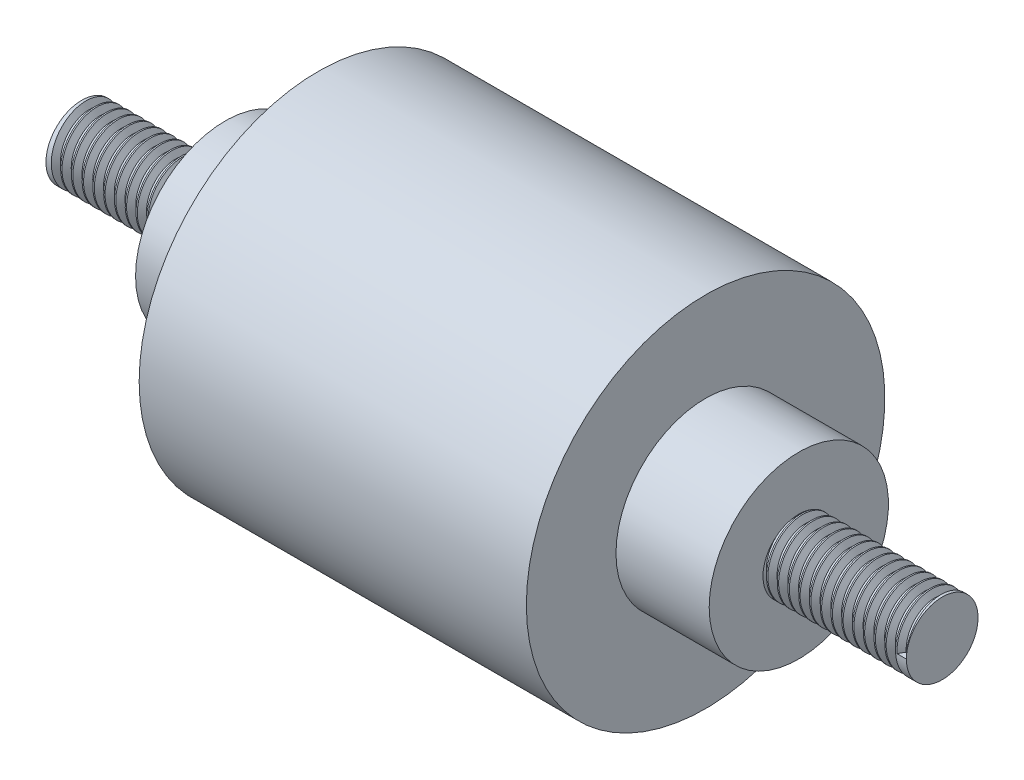
SolidWorks part; units mm, degrees
ref_plane "Front Plane" through (0, 0, 0) normal (0, 0, 1) x (1, 0, 0)
ref_plane "Top Plane" through (0, 0, 0) normal (0, 1, 0) x (1, 0, 0)
ref_plane "Right Plane" through (0, 0, 0) normal (1, 0, 0) x (0, 0, -1)
sketch "Sketch1" plane through (0, 0, 0) normal (0, 0, 1) x (1, 0, 0)
  line L0 (0, -64.1686) -> (0, 56.0058) construction
  line L1 (43.9884, 0) -> (-105.0581, 0) construction
  line L2 (-40, 0) -> (-40, 12.5)
  line L3 (-40, 12.5) -> (-27, 12.5)
  line L4 (-27, 12.5) -> (-27, 25)
  line L5 (-27, 25) -> (27, 25)
  line L6 (-40, 0) -> (40, 0)
  line L7 (40, 0) -> (40, 12.5)
  line L8 (40, 12.5) -> (27, 12.5)
  line L9 (27, 12.5) -> (27, 25)
  dimension "D1" = 13
  dimension "D2" = 25
  dimension "D3" = 54
  dimension "D4" = 50
revolve "Revolve1" add sketch "Sketch1" angle 360 about L6
sketch "Sketch2" plane through (40, 0, 0) normal (1, 0, 0) x (0, 0, -1)
  circle A0 centre (0, 0) radius 5
  dimension "D1" = 10
extrude "Boss-Extrude1" add sketch "Sketch2" along normal blind 20
thread "Thread1" pitch 1.5 start angle 0, offset 0, length 0, pitch 1.5, diameter 10
ref_plane "Plane1" through (60, 0, 5) normal (0, -1, 0) x (0, 0, 1)
sketch "Thread Profile1" plane through (60, 0, 5) normal (0, -1, 0) x (0, 0, 1)
  line L0 (0, 0) -> (0, 1.5) construction
  line L11 (0, 0) -> (0, 1.3125)
  line L12 (0, 1.3125) -> (-0.8119, 0.8437)
  line L13 (-0.8119, 0.8437) -> (-0.8119, 0.4687)
  line L15 (-0.8119, 0.4687) -> (0, 0)
  line L17 (-0.8119, 0.6562) -> (0, 0.6562) construction
  point P2 (0, 0)
  dimension "Pitch" = 1.5
  dimension "Profile_Angle" = 60
  dimension "Profile_Land" = 0.375
  dimension "Profile_Height" = 0.8119
mirror "Mirror3" about plane through (0, 0, 0) normal (1, 0, 0) of "Boss-Extrude1"
thread "Thread2" pitch 1.5 profile "Thread Profile2" start angle 0, offset 0, length 0, pitch 1.5, diameter 10
ref_plane "Plane2" through (-60, 0, -5) normal (0, -1, 0) x (0, 0, -1)
sketch "Thread Profile2" plane through (-60, 0, -5) normal (0, -1, 0) x (0, 0, -1)
  line L0 (0, 0) -> (0, 1.5) construction
  line L11 (0, 0) -> (0, 1.3125)
  line L12 (0, 1.3125) -> (-0.8119, 0.8437)
  line L13 (-0.8119, 0.8437) -> (-0.8119, 0.4687)
  line L15 (-0.8119, 0.4687) -> (0, 0)
  line L17 (-0.8119, 0.6562) -> (0, 0.6562) construction
  point P2 (0, 0)
  dimension "Pitch" = 1.5
  dimension "Profile_Angle" = 60
  dimension "Profile_Land" = 0.375
  dimension "Profile_Height" = 0.8119
sketch "Sketch10" plane through (0, 0, 0) normal (0, 1, 0) x (1, 0, 0)
  circle A0 centre (0, 0) radius 6.6652
extrude "Cut-Extrude1" cut sketch "Sketch10" against normal through all
